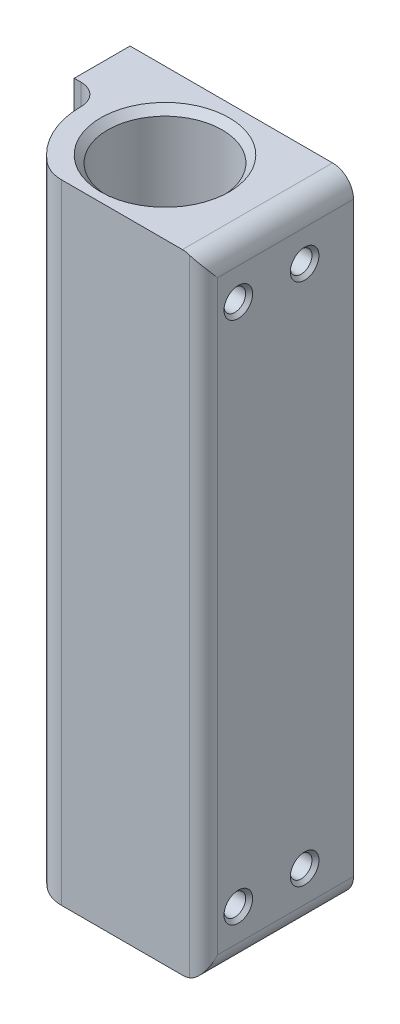
SolidWorks part; units mm, degrees
ref_plane "Front Plane" through (0, 0, 0) normal (0, 0, 1) x (1, 0, 0)
ref_plane "Top Plane" through (0, 0, 0) normal (0, 1, 0) x (1, 0, 0)
ref_plane "Right Plane" through (0, 0, 0) normal (1, 0, 0) x (0, 0, -1)
sketch "Sketch1" plane through (0, 0, 0) normal (0, 1, 0) x (1, 0, 0)
  line L1 (-16, 11) -> (16, 11)
  line L2 (-16, 11) -> (-16, 3)
  line L3 (-16, 3) -> (-15, 3)
  line L4 (16, 11) -> (16, -8.5)
  line L5 (-4.3301, -10.5) -> (14, -10.5)
  circle A0 centre (0, 0) radius 8.2
  arc A1 (-12, 0) -> (-7.4231, -9.4286) centre (0, 0) ccw
  arc A2 (14, -10.5) -> (16, -8.5) centre (14, -8.5) ccw
  arc A3 (-12, 0) -> (-15, 3) centre (-15, 0) ccw
  arc A6 (-4.3301, -10.5) -> (-7.4231, -9.4286) centre (-4.3301, -5.5) cw
  dimension "D1" = 16.4
  dimension "D2" = 12
  dimension "D6" = 3
  dimension "D8" = 5
  dimension "D10" = 2
  dimension "D3" = 32
  dimension "D4" = 8
  dimension "D5" = 11
  dimension "D7" = 10.5
  dimension "D9" = 16
extrude "Boss-Extrude1" add sketch "Sketch1" along normal blind 90
sketch "Sketch2" plane through (0, 0, -11) normal (0, 0, 1) x (1, 0, 0)
  line L0 (-11, 85) -> (11, 5) construction
  line L1 (0, 45) -> (0, 0) construction
  line L2 (-16, 45) -> (0, 45) construction
  line L3 (-16, 90) -> (-16, 0) construction
  line L5 (-4.3301, 90) -> (14, 90) construction
  circle A0 centre (-11, 85) radius 2.6
  circle A1 centre (-11, 5) radius 2.6
  circle A2 centre (11, 85) radius 2.6
  circle A3 centre (11, 5) radius 2.6
  dimension "D1" = 5.2
  dimension "D2" = 5
  dimension "D3" = 5
extrude "Cut-Extrude1" cut sketch "Sketch2" along normal blind 6
sketch "Sketch3" plane through (16, 0, 0) normal (1, 0, 0) x (0, 0, -1)
  line L0 (-8.5, 90) -> (11, 90) construction
  line L1 (-8.5, 0) -> (11, 0) construction
  line L2 (11, 90) -> (11, 0) construction
  circle A0 centre (-5.5, 82.5) radius 1.55
  circle A1 centre (4, 82.5) radius 1.55
  circle A2 centre (-5.5, 7.5) radius 1.55
  circle A3 centre (4, 7.5) radius 1.55
  dimension "D5" = 3.1
  dimension "D1" = 7.5
  dimension "D2" = 9.5
  dimension "D3" = 7.5
  dimension "D4" = 7
extrude "Cut-Extrude2" cut sketch "Sketch3" against normal blind 7
chamfer "Chamfer1" distance 0.5 angle 45 8 edges at (-8.4, 5, -11) (13.6, 5, -11) (13.6, 85, -11) (-8.4, 85, -11) (16, 7.5, -5.55) (16, 7.5, 3.95) (16, 82.5, -5.55) (16, 82.5, 3.95)
chamfer "Chamfer2" distance 1 angle 45 2 edges at (0, 0, 8.2) (0, 90, 8.2)
fillet "Fillet1" radius 3 2 edges at (16, 0, -1.25) (16, 90, -1.25) tangent propagation no
